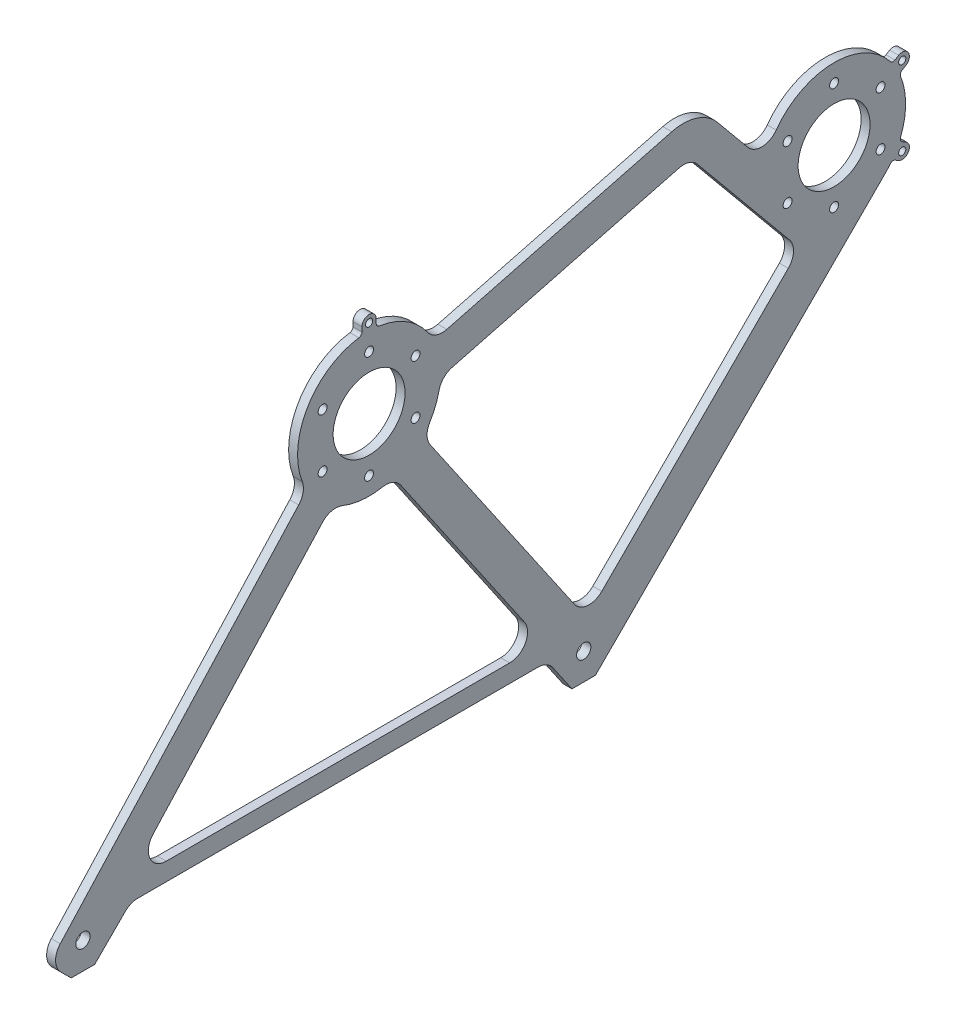
SolidWorks part; units mm, degrees
material "Stal węglowa"
ref_plane "Front" through (0, 0, 0) normal (0, 0, 1) x (1, 0, 0)
ref_plane "Top" through (0, 0, 0) normal (0, 1, 0) x (1, 0, 0)
ref_plane "Right" through (0, 0, 0) normal (1, 0, 0) x (0, 0, -1)
sketch "Szkic1" plane through (0, 0, 0) normal (1, 0, 0) x (0, 0, -1)
  line L0 (236.8738, 44.74) -> (75.1581, -116.9758)
  line L1 (75.1581, -116.9758) -> (62.021, -116.9758)
  line L2 (-164.8415, -86.9758) -> (27.1963, -86.9758)
  line L3 (143.4248, 116.6296) -> (160.4198, 96.0389)
  line L4 (-7.9808, 92.0995) -> (117.836, 124.9069)
  line L5 (-224.1072, -97.338) -> (-90.7652, 48.5048)
  line L6 (182.9859, 26.2074) -> (78.6855, -78.093)
  line L7 (-172.2218, -70.2281) -> (-77.4797, 33.3961)
  line L8 (62.021, -116.9758) -> (51.2859, -101.3205)
  line L9 (-223.798, -111.1568) -> (-217.979, -116.9758)
  line L10 (-204.8419, -116.9758) -> (-217.979, -116.9758)
  line L11 (-187.7709, -99.9047) -> (-204.8419, -116.9758)
  line L12 (43.0387, -96.9758) -> (-180.6998, -96.9758)
  line L13 (63.3672, -76.6772) -> (-17.2474, 40.8857)
  line L14 (35.4436, -71.3205) -> (-33.742, 29.5751)
  line L15 (246.5895, 55.7037) -> (248.6947, 54.4883)
  line L16 (242.5895, 48.7755) -> (244.6947, 47.5601)
  line L17 (246.5895, 90.3447) -> (248.6947, 91.5601)
  line L18 (242.5895, 97.273) -> (244.6947, 98.4883)
  line L19 (-55.4105, 114.5935) -> (-55.4105, 117.0242)
  line L20 (-47.4105, 114.5935) -> (-47.4105, 117.0242)
  line L21 (132.1649, 101.9946) -> (183.6272, 39.644)
  line L22 (-5.0498, 72.195) -> (121.9294, 105.3055)
  arc A0 (-66.3617, 35.9235) -> (-43.8735, 33.7407) centre (-51.4105, 73.0242) ccw
  circle A1 centre (234.5703, 58.0242) radius 2.5
  circle A2 centre (182.6088, 58.0242) radius 2.5
  circle A3 centre (208.5895, 43.0242) radius 2.5
  circle A4 centre (182.6088, 88.0242) radius 2.5
  circle A5 centre (208.5895, 103.0242) radius 2.5
  circle A6 centre (234.5703, 88.0242) radius 2.5
  circle A7 centre (-25.4297, 58.0242) radius 2.5
  circle A8 centre (-51.4105, 103.0242) radius 2.5
  circle A9 centre (-77.3912, 58.0242) radius 2.5
  circle A10 centre (-25.4297, 88.0242) radius 2.5
  circle A11 centre (-51.4105, 43.0242) radius 2.5
  circle A12 centre (-77.3912, 88.0242) radius 2.5
  circle A13 centre (-211.4105, -101.9758) radius 4
  circle A14 centre (68.5895, -101.9758) radius 4
  arc A15 (240.0181, 97.7678) -> (176.2236, 96.5284) centre (208.5895, 73.0242) ccw
  arc A16 (-90.7652, 48.5048) -> (-88.7985, 58.8069) centre (-98.1455, 55.2525) ccw
  arc A17 (-18.6853, 96.0256) -> (-7.9808, 92.0995) centre (-10.504, 101.776) ccw
  arc A18 (-224.1072, -97.338) -> (-223.798, -111.1568) centre (-216.7269, -104.0857) ccw
  arc A19 (-17.4822, 51.8376) -> (-12.3034, 64.6197) centre (-51.4105, 73.0242) ccw
  arc A20 (-66.3617, 35.9235) -> (-77.4797, 33.3961) centre (-70.0995, 26.6484) ccw
  arc A21 (-57.1248, 112.614) -> (-88.7985, 58.8069) centre (-51.4105, 73.0242) ccw
  arc A22 (51.2859, -101.3205) -> (43.0387, -96.9758) centre (43.0387, -106.9758) ccw
  arc A23 (-180.6998, -96.9758) -> (-187.7709, -99.9047) centre (-180.6998, -106.9758) ccw
  arc A24 (27.1963, -86.9758) -> (35.4436, -71.3205) centre (27.1963, -76.9758) ccw
  arc A25 (63.3672, -76.6772) -> (78.6855, -78.093) centre (71.6144, -71.0219) ccw
  arc A26 (-33.742, 29.5751) -> (-43.8735, 33.7407) centre (-41.9893, 23.9198) ccw
  arc A27 (-17.4822, 51.8376) -> (-17.2474, 40.8857) centre (-9.0001, 46.541) ccw
  circle A28 centre (246.6947, 95.0242) radius 2
  arc A29 (240.0181, 97.7678) -> (242.5895, 97.273) centre (241.5895, 99.005) ccw
  arc A30 (245.7324, 58.1781) -> (245.7324, 87.8704) centre (208.5895, 73.0242) ccw
  arc A31 (248.6947, 91.5601) -> (244.6947, 98.4883) centre (246.6947, 95.0242) ccw
  arc A32 (236.8738, 44.74) -> (240.0181, 48.2807) centre (208.5895, 73.0242) ccw
  arc A33 (242.5895, 48.7755) -> (240.0181, 48.2807) centre (241.5895, 47.0435) ccw
  circle A34 centre (246.6947, 51.0242) radius 2
  arc A35 (244.6947, 47.5601) -> (248.6947, 54.4883) centre (246.6947, 51.0242) ccw
  arc A36 (245.7324, 58.1781) -> (246.5895, 55.7037) centre (247.5895, 57.4358) ccw
  arc A37 (246.5895, 90.3447) -> (245.7324, 87.8704) centre (247.5895, 88.6127) ccw
  arc A38 (-47.4105, 114.5935) -> (-45.6962, 112.614) centre (-45.4105, 114.5935) ccw
  circle A39 centre (-51.4105, 117.0242) radius 2
  arc A40 (-47.4105, 117.0242) -> (-55.4105, 117.0242) centre (-51.4105, 117.0242) ccw
  arc A41 (-57.1248, 112.614) -> (-55.4105, 114.5935) centre (-57.4105, 114.5935) ccw
  arc A42 (-18.6853, 96.0256) -> (-45.6962, 112.614) centre (-51.4105, 73.0242) ccw
  arc A43 (182.9859, 26.2074) -> (183.6272, 39.644) centre (175.9148, 33.2785) ccw
  arc A44 (-172.2218, -70.2281) -> (-164.8415, -86.9758) centre (-164.8415, -76.9758) ccw
  arc A45 (132.1649, 101.9946) -> (121.9294, 105.3055) centre (124.4525, 95.6291) ccw
  arc A46 (-5.0498, 72.195) -> (-12.3034, 64.6197) centre (-2.5266, 62.5186) ccw
  circle A47 centre (-51.4105, 73.0242) radius 20.1
  circle A48 centre (208.5895, 73.0242) radius 20.1
  arc A49 (143.4248, 116.6296) -> (117.836, 124.9069) centre (124.144, 100.7158) ccw
  arc A50 (160.4198, 96.0389) -> (176.2236, 96.5284) centre (168.1321, 102.4044) ccw
extrude "Dodanie-wyciągnięcie1" add sketch "Szkic1" along normal blind 5
